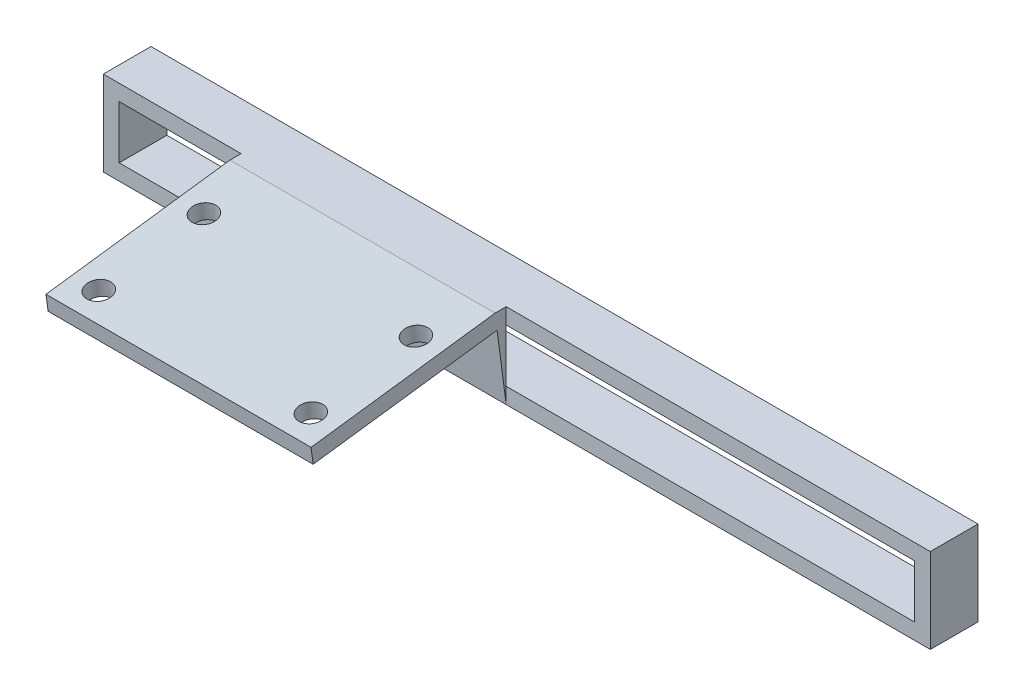
SolidWorks part; units mm, degrees
ref_plane "Top Plane" through (0, 0, 0) normal (0, 0, 1) x (1, 0, 0)
ref_plane "Front Plane" through (0, 0, 0) normal (0, 1, 0) x (1, 0, 0)
ref_plane "Right Plane" through (0, 0, 0) normal (1, 0, 0) x (0, 0, -1)
sketch "Sketch1" plane through (0, 0, 0) normal (0, 0, 1) x (1, 0, 0)
  line L1 (0, 0) -> (156, 0)
  line L2 (0, 0) -> (0, 16)
  line L3 (0, 16) -> (156, 16)
  line L4 (156, 0) -> (156, 16)
  dimension "D1" = 156
  dimension "D2" = 16
extrude "Boss-Extrude1" add sketch "Sketch1" along normal blind 9
sketch "Sketch2" plane through (0, 0, 9) normal (0, 0, 1) x (1, 0, 0)
  line L14 (153, 3) -> (153, 13)
  line L15 (3, 3) -> (153, 3)
  line L16 (3, 13) -> (3, 3)
  line L17 (153, 13) -> (3, 13)
  line L18 (153, 3) -> (153, 13)
  line L19 (3, 3) -> (153, 3)
  line L20 (3, 13) -> (3, 3)
  line L21 (153, 13) -> (3, 13)
  dimension "D1" = 3
extrude "Cut-Extrude1" cut sketch "Sketch2" against normal blind 9
sketch "Sketch4" plane through (156, 0, 0) normal (1, 0, 0) x (0, 0, -1)
  line L0 (-9, 16) -> (-11.1064, 16)
  line L1 (-11.1064, 16) -> (-9, 0)
  line L2 (-9, 0) -> (-9, 16)
  dimension "D1" = 7.5
extrude "Boss-Extrude2" add sketch "Sketch4" along normal blind 50 from offset 130 offset against normal yes
sketch "Sketch5" plane through (0, -1.1647, 8.8467) normal (0, -0.1305, 0.9914) x (1, 0, 0)
  line L0 (76, 17.3128) -> (76, 1.1747) construction
  line L1 (26, 17.3128) -> (76, 17.3128)
  line L2 (26, 17.3128) -> (26, 14.3128)
  line L3 (26, 14.3128) -> (76, 14.3128)
  line L4 (76, 17.3128) -> (76, 14.3128)
  line L6 (76, 17.3128) -> (26, 17.3128) construction
  line L7 (26, 17.3128) -> (26, 1.1747) construction
  dimension "D1" = 3
extrude "Boss-Extrude3" add sketch "Sketch5" along normal blind 35
sketch "Sketch6" plane through (0, 17.1647, 2.2598) normal (0, 0.9914, 0.1305) x (1, 0, 0)
  line L0 (76, -8.923) -> (26, -8.923) construction
  line L1 (31, -18.923) -> (71, -18.923)
  line L2 (31, -18.923) -> (31, -38.923)
  line L3 (31, -38.923) -> (71, -38.923)
  line L4 (71, -18.923) -> (71, -38.923)
  line L5 (26, -43.923) -> (26, -8.923) construction
  dimension "D1" = 40
  dimension "D2" = 20
  dimension "D3" = 10
  dimension "D4" = 5
hole_wizard "M4 Clearance Hole1" positions "Sketch7" profile "Sketch8" hole size "M4" standard "DIN" end condition through all
sketch "Sketch7" plane through (0, 17.1647, 2.2598) normal (0, 0.9914, 0.1305) x (1, 0, 0)
  point P0 (31, -18.923)
  point P3 (71, -18.923)
  point P6 (71, -38.923)
  point P9 (31, -38.923)
sketch "Sketch8" plane through (31, 14.6947, 21.0209) normal (1, 0, 0) x (0, -0.1305, 0.9914)
  line L0 (0, 0) -> (0, 17.3128)
  line L1 (0, 17.3128) -> (2.25, 17.3128)
  line L2 (2.25, 17.3128) -> (2.25, 0)
  line L5 (2.25, 0) -> (0, 0)
  line L11 (0, -6.35) -> (0, 107.95) construction
  dimension "Thru Hole Dia." = 4.5
  dimension "Thru Hole Depth" = 17.3128
